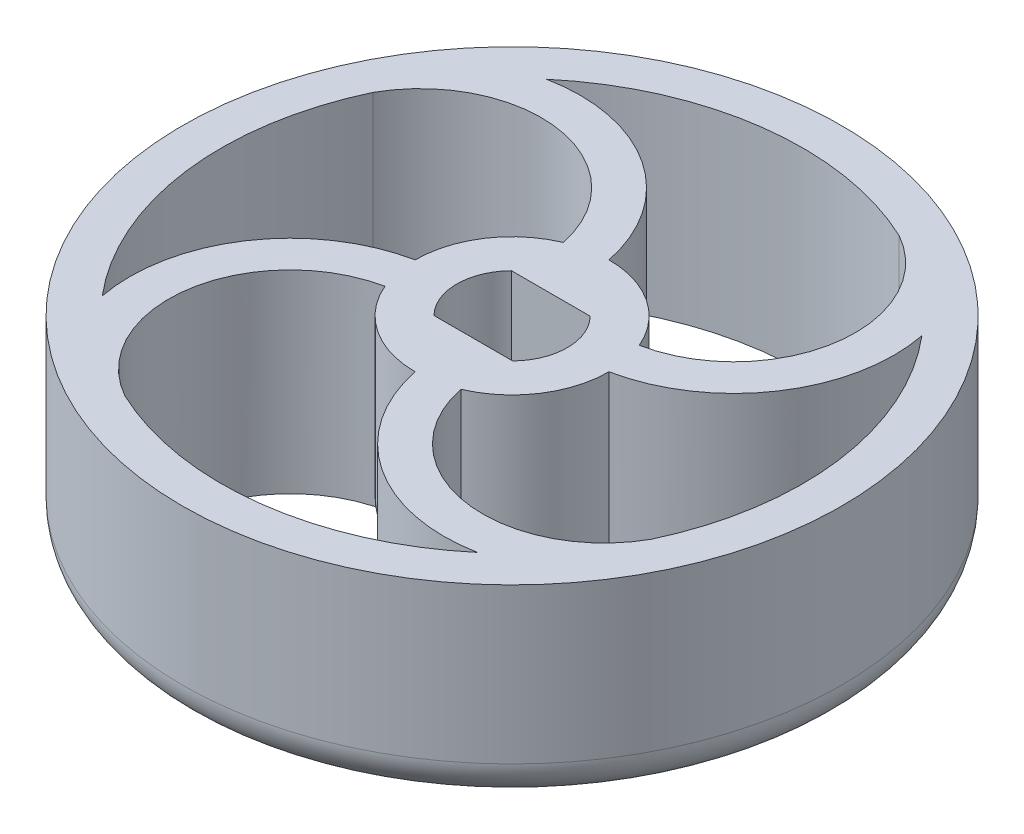
SolidWorks part; units mm, degrees
ref_plane "Front Plane" through (0, 0, 0) normal (0, 0, 1) x (1, 0, 0)
ref_plane "Top Plane" through (0, 0, 0) normal (0, 1, 0) x (1, 0, 0)
ref_plane "Right Plane" through (0, 0, 0) normal (1, 0, 0) x (0, 0, -1)
sketch "Sketch1" plane through (0, 0, 0) normal (0, 1, 0) x (1, 0, 0)
  circle A0 centre (0, 0) radius 15
  circle A1 centre (0, 0) radius 17
  dimension "D1" = 30
  dimension "D2" = 34
extrude "Boss-Extrude1" add sketch "Sketch1" along normal blind 10
sketch "Sketch2" plane through (0, 10, 0) normal (0, 1, 0) x (1, 0, 0)
  line L0 (-1.9449, 1.8) -> (1.9449, 1.8)
  line L1 (-1.9449, -1.8) -> (1.9449, -1.8)
  circle A0 centre (0, 0) radius 5
  arc A1 (-1.9449, 1.8) -> (-1.9449, -1.8) centre (0, 0) ccw
  arc A2 (1.9449, -1.8) -> (1.9449, 1.8) centre (0, 0) ccw
  dimension "D1" = 10
  dimension "D2" = 5.3
  dimension "D3" = 3.6
  dimension "D4" = 1.8
extrude "Boss-Extrude2" add sketch "Sketch2" against normal blind 10 separate body
sketch "Sketch3" plane through (0, 10, 0) normal (0, 1, 0) x (1, 0, 0)
  arc A0 (-13.5661, 6.4) -> (-1.9596, 4.6) centre (-8.0967, 3.3473) cw
  circle A1 centre (0, 0) radius 15 construction
  circle A2 centre (0, 0) radius 5 construction
  arc A3 (-9.681, 11.4577) -> (0, 5) centre (-8.0967, 3.3473) cw
  arc A4 (-9.681, 11.4577) -> (-13.5661, 6.4) centre (0, 0) ccw
  arc A5 (0, 5) -> (-1.9596, 4.6) centre (0, 0) ccw
  arc A6 (-10.1676, 9.2587) -> (-1.9596, 4.6) centre (-8.0967, 3.3473) cw construction
  arc A7 (-10.8288, 11.1463) -> (0, 5) centre (-8.0967, 3.3473) cw construction
  arc A8 (6.4, 13.5661) -> (4.6, 1.9596) centre (3.3473, 8.0967) cw
  arc A9 (11.4577, 9.681) -> (6.4, 13.5661) centre (0, 0) ccw
  arc A10 (11.4577, 9.681) -> (5, 0) centre (3.3473, 8.0967) cw
  arc A11 (5, 0) -> (4.6, 1.9596) centre (0, 0) ccw
  arc A12 (13.5661, -6.4) -> (1.9596, -4.6) centre (8.0967, -3.3473) cw
  arc A13 (9.681, -11.4577) -> (13.5661, -6.4) centre (0, 0) ccw
  arc A14 (9.681, -11.4577) -> (0, -5) centre (8.0967, -3.3473) cw
  arc A15 (0, -5) -> (1.9596, -4.6) centre (0, 0) ccw
  arc A16 (-6.4, -13.5661) -> (-4.6, -1.9596) centre (-3.3473, -8.0967) cw
  arc A17 (-11.4577, -9.681) -> (-6.4, -13.5661) centre (0, 0) ccw
  arc A18 (-11.4577, -9.681) -> (-5, 0) centre (-3.3473, -8.0967) cw
  arc A19 (-5, 0) -> (-4.6, -1.9596) centre (0, 0) ccw
  point P32 (0, 0)
  dimension "D2" = 6.4
  dimension "D1" = 2
  dimension "D3" = 4
extrude "Boss-Extrude3" add sketch "Sketch3" against normal blind 10
fillet "Fillet1" radius 2 1 edges at (0, 0, 17)
sketch "Sketch4" plane through (0, 0, 0) normal (0, -1, 0) x (1, 0, 0)
  line L0 (-1.9449, 1.8) -> (1.9449, 1.8) construction
  line L1 (-1.9449, 1.8) -> (1.9449, 1.8)
  line L2 (1.9449, -1.8) -> (-1.9449, -1.8) construction
  line L3 (1.9449, -1.8) -> (-1.9449, -1.8)
  arc A0 (1.9449, -1.8) -> (1.9449, 1.8) centre (0, 0) ccw construction
  arc A1 (1.9449, -1.8) -> (1.9449, 1.8) centre (0, 0) ccw
  arc A2 (-1.9449, 1.8) -> (-1.9449, -1.8) centre (0, 0) ccw construction
  arc A3 (-1.9449, 1.8) -> (-1.9449, -1.8) centre (0, 0) ccw
extrude "Boss-Extrude4" add sketch "Sketch4" against normal blind 2
fillet "Fillet2" radius 2 4 edges at (2.757, 0, -4.1712) (4.1712, 0, 2.757) (-2.757, 0, 4.1712) (-4.1712, 0, -2.757)
sketch "Sketch5" plane through (0, 10, 0) normal (0, 1, 0) x (1, 0, 0)
  line L7 (-2.0304, -2) -> (2.0304, -2)
  line L8 (2.0304, 2) -> (-2.0304, 2)
  line L9 (-2.0304, -2) -> (2.0304, -2)
  line L10 (2.0304, 2) -> (-2.0304, 2)
  arc A7 (2.0304, -2) -> (2.0304, 2) centre (0, 0) ccw
  arc A8 (-2.0304, 2) -> (-2.0304, -2) centre (0, 0) ccw
  arc A9 (2.0304, -2) -> (2.0304, 2) centre (0, 0) ccw
  arc A10 (-2.0304, 2) -> (-2.0304, -2) centre (0, 0) ccw
  dimension "D1" = 0.2
extrude "Cut-Extrude1" cut sketch "Sketch5" against normal blind 8
